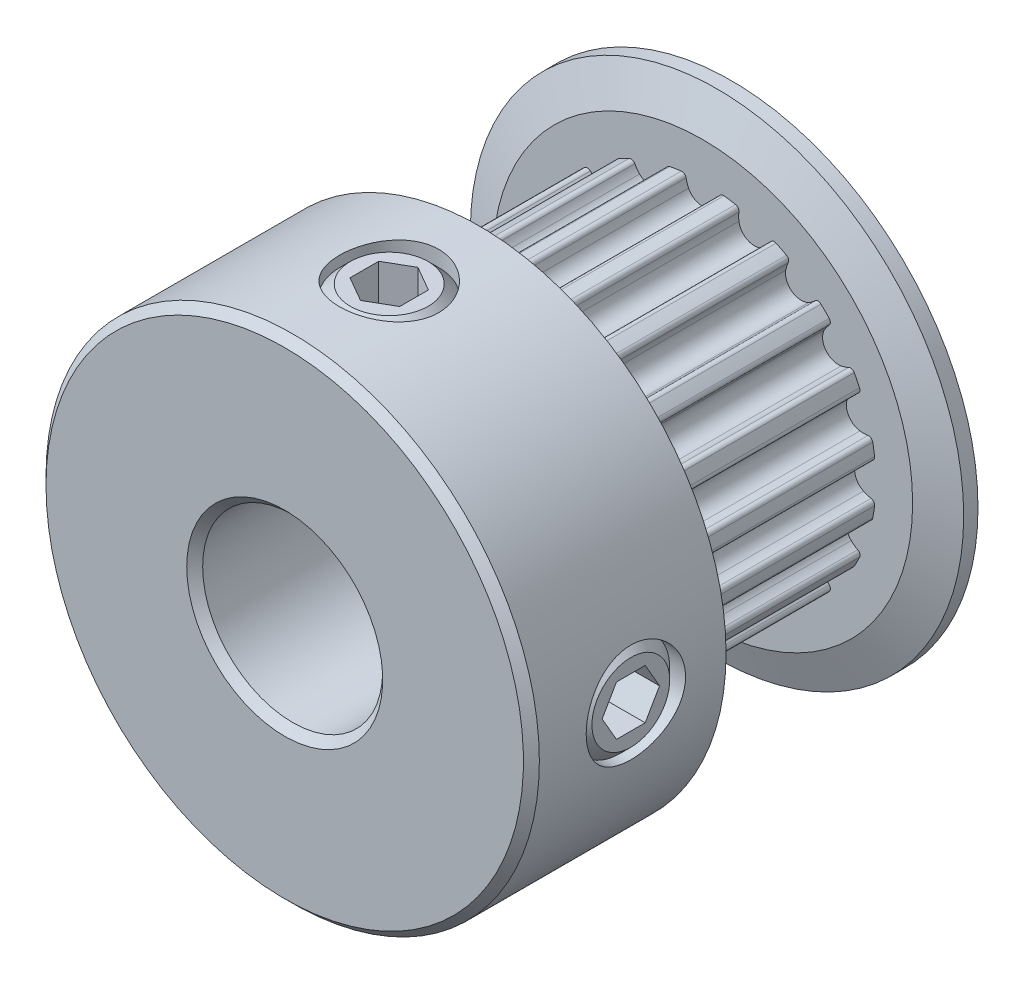
SolidWorks part; units mm, degrees
ref_plane "Front Plane" through (0, 0, 0) normal (0, 0, 1) x (1, 0, 0)
ref_plane "Top Plane" through (0, 0, 0) normal (0, 1, 0) x (1, 0, 0)
ref_plane "Right Plane" through (0, 0, 0) normal (1, 0, 0) x (0, 0, -1)
sketch "Sketch1" plane through (0, 0, 0) normal (0, 0, 1) x (1, 0, 0)
  line L1 (-1.7499, 5.3585) -> (1.7499, 5.3585) construction
  line L4 (0, 0) -> (0, 5.3585) construction
  line L5 (0, 5.3585) -> (0, 11.2112) construction
  line L6 (0, 6.3625) -> (1.9751, 6.0482) construction
  line L7 (1.9751, 6.0482) -> (2.6648, 5.8229) construction
  line L8 (1.9751, 6.0482) -> (1.7499, 5.3585) construction
  line L9 (-1.9751, 6.0482) -> (-1.7499, 5.3585) construction
  line L10 (-1.8963, 5.8067) -> (-2.841, 8.6995)
  line L11 (-2.841, 8.6995) -> (2.841, 8.6995)
  line L12 (2.841, 8.6995) -> (1.8963, 5.8067)
  circle A0 centre (0, 0) radius 6.3625 construction
  circle A1 centre (0, 0) radius 8.6995 construction
  circle A2 centre (0, 0) radius 6.1085 construction
  arc A3 (-0.4989, 5.6703) -> (0.4989, 5.6703) centre (0, 5.9135) ccw
  arc A4 (-0.4989, 5.6703) -> (-0.5855, 5.9387) centre (0.4, 6.1085) cw
  arc A5 (-1.8963, 5.8067) -> (-0.7518, 6.0621) centre (0, 0) cw
  arc A6 (-0.5855, 5.9387) -> (-0.7518, 6.0621) centre (-0.7333, 5.9132) ccw
  arc A7 (1.8963, 5.8067) -> (0.7518, 6.0621) centre (0, 0) ccw
  arc A8 (0.5855, 5.9387) -> (0.7518, 6.0621) centre (0.7333, 5.9132) cw
  arc A9 (0.4989, 5.6703) -> (0.5855, 5.9387) centre (-0.4, 6.1085) ccw
  point P6 (0, 20.9083)
  point P11 (0, 6.3625)
  point P13 (0, 8.6995)
  point P14 (0, 6.1085)
  dimension "D1" = 9.6972
  dimension "D2" = 4.8487
sketch "Sketch2" plane through (0, 0, 0) normal (1, 0, 0) x (0, 0, -1)
  line L0 (-7.875, 3.175) -> (7.875, 3.175)
  line L1 (-7.875, 3.175) -> (-7.875, 8.6995)
  line L2 (-1.01, 8.6995) -> (-7.875, 8.6995)
  line L3 (-1.515, 3.175) -> (-1.515, 8.6995) construction
  line L4 (-1.515, 8.6995) -> (-0.505, 8.6995) construction
  line L5 (-0.505, 8.6995) -> (-0.505, 6.1085) construction
  line L6 (-0.505, 6.1085) -> (6.865, 6.1085)
  line L7 (6.865, 6.1085) -> (6.865, 8.6995) construction
  line L8 (6.865, 8.6995) -> (7.875, 8.6995) construction
  line L9 (7.875, 8.6995) -> (7.875, 3.175)
  line L10 (-7.875, 0) -> (7.875, 0) construction
  line L11 (7.37, 8.6995) -> (6.865, 7.404)
  line L12 (-0.505, 7.404) -> (-1.01, 8.6995)
  line L14 (-0.505, 7.404) -> (-0.505, 6.1085)
  line L15 (6.865, 6.1085) -> (6.865, 7.404)
  line L16 (7.37, 8.6995) -> (7.875, 8.6995)
  arc A0 (-0.505, 7.404) -> (-1.01, 8.6995) centre (-2.4192, 7.404) ccw construction
  arc A1 (6.865, 7.404) -> (7.37, 8.6995) centre (8.7792, 7.404) cw construction
  point P12 (-0.505, 7.404)
  point P14 (-1.01, 8.6995)
  point P20 (6.865, 7.404)
  point P21 (7.37, 8.6995)
  point P25 (6.865, 0)
  point P26 (-0.505, 0)
  dimension "OA" = 15.75
  dimension "Bore" = 6.35
  dimension "Outside Width" = 8.38
  dimension "Inside Width" = 7.37
revolve "Revolve1" add sketch "Sketch2" angle 360 mid plane about L10
sketch "Sketch3" plane through (0, 0, 0) normal (0, 0, 1) x (1, 0, 0)
  line L6 (2.841, 8.6995) -> (-2.841, 8.6995)
  line L7 (1.8963, 5.8067) -> (2.841, 8.6995)
  line L8 (-2.841, 8.6995) -> (-1.8963, 5.8067)
  line L9 (2.841, 8.6995) -> (-2.841, 8.6995)
  line L10 (1.8963, 5.8067) -> (2.841, 8.6995)
  line L11 (-2.841, 8.6995) -> (-1.8963, 5.8067)
  arc A8 (1.8963, 5.8067) -> (0.7518, 6.0621) centre (0, 0) ccw
  arc A9 (0.7518, 6.0621) -> (0.5855, 5.9387) centre (0.7333, 5.9132) ccw
  arc A10 (0.4989, 5.6703) -> (0.5855, 5.9387) centre (-0.4, 6.1085) ccw
  arc A11 (-0.4989, 5.6703) -> (0.4989, 5.6703) centre (0, 5.9135) ccw
  arc A12 (-0.5855, 5.9387) -> (-0.4989, 5.6703) centre (0.4, 6.1085) ccw
  arc A13 (-0.5855, 5.9387) -> (-0.7518, 6.0621) centre (-0.7333, 5.9132) ccw
  arc A14 (-0.7518, 6.0621) -> (-1.8963, 5.8067) centre (0, 0) ccw
  arc A15 (1.8963, 5.8067) -> (0.7518, 6.0621) centre (0, 0) ccw
  arc A16 (0.7518, 6.0621) -> (0.5855, 5.9387) centre (0.7333, 5.9132) ccw
  arc A17 (0.4989, 5.6703) -> (0.5855, 5.9387) centre (-0.4, 6.1085) ccw
  arc A18 (-0.4989, 5.6703) -> (0.4989, 5.6703) centre (0, 5.9135) ccw
  arc A19 (-0.5855, 5.9387) -> (-0.4989, 5.6703) centre (0.4, 6.1085) ccw
  arc A20 (-0.5855, 5.9387) -> (-0.7518, 6.0621) centre (-0.7333, 5.9132) ccw
  arc A21 (-0.7518, 6.0621) -> (-1.8963, 5.8067) centre (0, 0) ccw
  dimension "D1" = 0
extrude "Cut-Extrude1" cut sketch "Sketch3" against normal up to vertex (6.865 mm away) from vertex up to point (0, 6.1085, -6.865) starting at point (0, 6.1085, 0.505)
pattern_circular "CirPattern1" count 20 over 360 about axis through (0, 0, 7.875) along (0, 0, 1) of "Cut-Extrude1"
sketch "Sketch4" plane through (0, 0, 0) normal (1, 0, 0) x (0, -1, 0)
  line L0 (0, -0.505) -> (0, -7.875) construction
  line L1 (-3.175, -7.875) -> (3.175, -7.875) construction
  line L2 (7.404, -0.505) -> (-7.404, -0.505) construction
  circle A0 centre (0, -4.19) radius 1.7526
extrude "Cut-Extrude2" cut sketch "Sketch4" along normal through all
ref_plane "Plane1" through (0, 0, 4.19) normal (0, 0, 1) x (1, 0, 0)
sketch "Sketch5" plane through (0, 0, 4.19) normal (0, 0, 1) x (1, 0, 0)
  line L0 (0, 0) -> (0, 8.6995) construction
  line L1 (3.175, -1.3716) -> (3.175, 0)
  line L2 (3.556, -1.7526) -> (8.1401, -1.7526)
  line L3 (3.175, 0) -> (8.6995, 0) construction
  line L4 (3.175, 0) -> (8.5211, 0)
  line L5 (8.5211, 0) -> (8.5211, -1.3716)
  line L6 (3.556, -1.7526) -> (3.175, -1.3716)
  line L7 (8.5211, -1.3716) -> (8.1401, -1.7526)
  circle A0 centre (0, 0) radius 8.6995 construction
  circle A1 centre (0, 0) radius 3.175 construction
  point P2 (3.175, -1.7526)
  point P11 (8.5211, -1.7526)
revolve "Revolve2" add sketch "Sketch5" angle 360 mid plane about L4
sketch "Sketch6" plane through (8.5211, 5.3841, 0) normal (-1, 0, 0) x (0, -1, 0)
  line L1 (5.3841, 5.2019) -> (4.5078, 4.6959)
  line L2 (4.5078, 4.6959) -> (4.5078, 3.6841)
  line L3 (4.5078, 3.6841) -> (5.3841, 3.1781)
  line L4 (5.3841, 3.1781) -> (6.2604, 3.6841)
  line L5 (6.2604, 3.6841) -> (6.2604, 4.6959)
  line L6 (6.2604, 4.6959) -> (5.3841, 5.2019)
  circle A0 centre (5.3841, 4.19) radius 0.8763 construction
  dimension "D1" = 1.7526
extrude "Cut-Extrude3" cut sketch "Sketch6" along normal blind 1.3144
pattern_circular "CirPattern3" count 2 over 90 about axis through (0, 0, 7.875) along (0, 0, 1) of "Cut-Extrude2", "Revolve2", "Cut-Extrude3"
chamfer "Chamfer1" distance 0.2807 angle 45 2 edges at (3.175, 0, 7.875) (8.6995, 0, 7.875)
ref_axis "Center Axis 1" through (0, 0, -7.875) along (0, 0, 1)
ref_plane "Contact Plane 1" through (0, 0, 7.875) normal (0, 0, 1) x (1, 0, 0)
ref_plane "Contact Plane 2" through (0, 0, -7.875) normal (0, 0, -1) x (-1, 0, 0)
equation "\"D2@Sketch1\"= \"D1@Sketch1\" / 2"
equation "\"D1@Sketch6\" = \"Set Screw@Sketch4\" / 2"
equation "\"D1@Cut-Extrude3\" = \"D1@Sketch6\"*.75"
